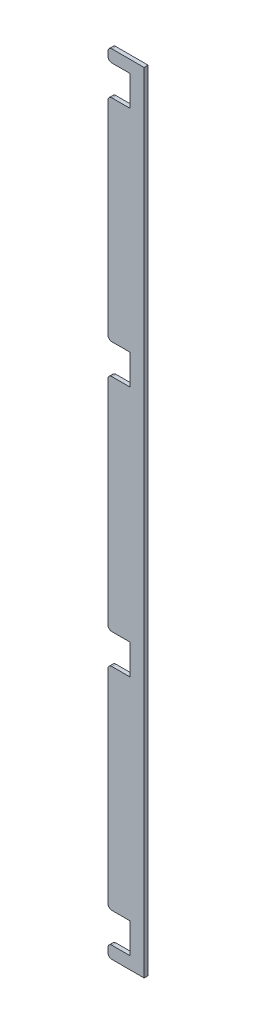
SolidWorks part; units mm, degrees
ref_plane "Front Plane" through (0, 0, 0) normal (0, 0, 1) x (1, 0, 0)
ref_plane "Top Plane" through (0, 0, 0) normal (0, 1, 0) x (1, 0, 0)
ref_plane "Right Plane" through (0, 0, 0) normal (1, 0, 0) x (0, 0, -1)
sketch "Sketch1" plane through (0, 0, 0) normal (0, 0, 1) x (1, 0, 0)
  line L0 (0, -182.5952) -> (-4.5, -182.5952)
  line L2 (0, 13.4048) -> (0, -182.5952)
  line L6 (-4.5, 10.3548) -> (-3.5, 10.3548)
  line L7 (-3.5, 10.3548) -> (-3.5, 2.8548)
  line L8 (0, 2.4048) -> (0, -6.5952) construction
  line L9 (-3.5, 2.8548) -> (-4.5, 2.8548)
  line L10 (-4.5, -49.6452) -> (-3.5, -49.6452)
  line L11 (-3.5, -49.6452) -> (-3.5, -57.1452)
  line L12 (-3.5, -57.1452) -> (-4.5, -57.1452)
  line L13 (-4.5, -112.0452) -> (-3.5, -112.0452)
  line L14 (-3.5, -112.0452) -> (-3.5, -119.5452)
  line L15 (-3.5, -119.5452) -> (-4.5, -119.5452)
  line L16 (-4.5, -172.0452) -> (-3.5, -172.0452)
  line L17 (-3.5, -172.0452) -> (-3.5, -179.5452)
  line L18 (-3.5, -179.5452) -> (-4.5, -179.5452)
  line L100 (-8, 10.3548) -> (-4.5, 10.3548)
  line L101 (-4.5, 10.3548) -> (-4.5, 2.8548)
  line L102 (-4.5, 2.8548) -> (-8, 2.8548)
  line L103 (-9, 1.8548) -> (-9, -48.6452)
  line L104 (-8, -49.6452) -> (-4.5, -49.6452)
  line L105 (-4.5, -49.6452) -> (-4.5, -57.1452)
  line L106 (-4.5, -57.1452) -> (-8, -57.1452)
  line L107 (-9, -58.1452) -> (-9, -111.0452)
  line L108 (-8, -112.0452) -> (-4.5, -112.0452)
  line L109 (-4.5, -112.0452) -> (-4.5, -119.5452)
  line L110 (-4.5, -119.5452) -> (-8, -119.5452)
  line L111 (-9, -120.5452) -> (-9, -171.0452)
  line L112 (-8, -172.0452) -> (-4.5, -172.0452)
  line L113 (-4.5, -172.0452) -> (-4.5, -179.5452)
  line L114 (-4.5, -179.5452) -> (-8, -179.5452)
  line L115 (-9, -180.5452) -> (-9, -181.5952)
  line L116 (-8, -182.5952) -> (-4.5, -182.5952)
  line L117 (-4.5, -182.5952) -> (-4.5, -191.5952)
  line L118 (-4.5, -191.5952) -> (78.5, -191.5952)
  line L119 (78.5, -191.5952) -> (78.5, -182.5952)
  line L120 (78.5, -182.5952) -> (82, -182.5952)
  line L121 (83, -181.5952) -> (83, -180.5452)
  line L122 (82, -179.5452) -> (78.5, -179.5452)
  line L123 (78.5, -179.5452) -> (78.5, -172.0452)
  line L124 (78.5, -172.0452) -> (82, -172.0452)
  line L125 (83, -171.0452) -> (83, -120.5452)
  line L126 (82, -119.5452) -> (78.5, -119.5452)
  line L127 (78.5, -119.5452) -> (78.5, -112.0452)
  line L128 (78.5, -112.0452) -> (82, -112.0452)
  line L129 (83, -111.0452) -> (83, -58.1452)
  line L130 (82, -57.1452) -> (78.5, -57.1452)
  line L131 (78.5, -57.1452) -> (78.5, -49.6452)
  line L132 (78.5, -49.6452) -> (82, -49.6452)
  line L133 (83, -48.6452) -> (83, 1.8548)
  line L134 (82, 2.8548) -> (78.5, 2.8548)
  line L135 (78.5, 2.8548) -> (78.5, 10.3548)
  line L136 (78.5, 10.3548) -> (82, 10.3548)
  line L137 (83, 11.3548) -> (83, 12.4048)
  line L138 (82, 13.4048) -> (78.5, 13.4048)
  line L139 (78.5, 13.4048) -> (78.5, 22.4048)
  line L140 (78.5, 22.4048) -> (-4.5, 22.4048)
  line L141 (-4.5, 22.4048) -> (-4.5, 13.4048)
  line L142 (-4.5, 13.4048) -> (-8, 13.4048)
  line L143 (-9, 12.4048) -> (-9, 11.3548)
  line L144 (-8, 10.3548) -> (-4.5, 10.3548)
  line L145 (-4.5, 10.3548) -> (-4.5, 2.8548)
  line L146 (-4.5, 2.8548) -> (-8, 2.8548)
  line L147 (-9, 1.8548) -> (-9, -48.6452)
  line L148 (-8, -49.6452) -> (-4.5, -49.6452)
  line L149 (-4.5, -49.6452) -> (-4.5, -57.1452)
  line L150 (-4.5, -57.1452) -> (-8, -57.1452)
  line L151 (-9, -58.1452) -> (-9, -111.0452)
  line L152 (-8, -112.0452) -> (-4.5, -112.0452)
  line L153 (-4.5, -112.0452) -> (-4.5, -119.5452)
  line L154 (-4.5, -119.5452) -> (-8, -119.5452)
  line L155 (-9, -120.5452) -> (-9, -171.0452)
  line L156 (-8, -172.0452) -> (-4.5, -172.0452)
  line L157 (-4.5, -172.0452) -> (-4.5, -179.5452)
  line L158 (-4.5, -179.5452) -> (-8, -179.5452)
  line L159 (-9, -180.5452) -> (-9, -181.5952)
  line L160 (-8, -182.5952) -> (-4.5, -182.5952)
  line L186 (0, 13.4048) -> (-8, 13.4048)
  line L187 (-9, 12.4048) -> (-9, 11.3548)
  arc A40 (-8, 2.8548) -> (-9, 1.8548) centre (-8, 1.8548) ccw
  arc A41 (-9, -48.6452) -> (-8, -49.6452) centre (-8, -48.6452) ccw
  arc A42 (-8, -57.1452) -> (-9, -58.1452) centre (-8, -58.1452) ccw
  arc A43 (-9, -111.0452) -> (-8, -112.0452) centre (-8, -111.0452) ccw
  arc A44 (-8, -119.5452) -> (-9, -120.5452) centre (-8, -120.5452) ccw
  arc A45 (-9, -171.0452) -> (-8, -172.0452) centre (-8, -171.0452) ccw
  arc A46 (-8, -179.5452) -> (-9, -180.5452) centre (-8, -180.5452) ccw
  arc A47 (-9, -181.5952) -> (-8, -182.5952) centre (-8, -181.5952) ccw
  arc A48 (82, -182.5952) -> (83, -181.5952) centre (82, -181.5952) ccw
  arc A49 (83, -180.5452) -> (82, -179.5452) centre (82, -180.5452) ccw
  arc A50 (82, -172.0452) -> (83, -171.0452) centre (82, -171.0452) ccw
  arc A51 (83, -120.5452) -> (82, -119.5452) centre (82, -120.5452) ccw
  arc A52 (82, -112.0452) -> (83, -111.0452) centre (82, -111.0452) ccw
  arc A53 (83, -58.1452) -> (82, -57.1452) centre (82, -58.1452) ccw
  arc A54 (82, -49.6452) -> (83, -48.6452) centre (82, -48.6452) ccw
  arc A55 (83, 1.8548) -> (82, 2.8548) centre (82, 1.8548) ccw
  arc A56 (82, 10.3548) -> (83, 11.3548) centre (82, 11.3548) ccw
  arc A57 (83, 12.4048) -> (82, 13.4048) centre (82, 12.4048) ccw
  arc A58 (-8, 13.4048) -> (-9, 12.4048) centre (-8, 12.4048) ccw
  arc A59 (-9, 11.3548) -> (-8, 10.3548) centre (-8, 11.3548) ccw
  arc A60 (-8, 2.8548) -> (-9, 1.8548) centre (-8, 1.8548) ccw
  arc A61 (-9, -48.6452) -> (-8, -49.6452) centre (-8, -48.6452) ccw
  arc A62 (-8, -57.1452) -> (-9, -58.1452) centre (-8, -58.1452) ccw
  arc A63 (-9, -111.0452) -> (-8, -112.0452) centre (-8, -111.0452) ccw
  arc A64 (-8, -119.5452) -> (-9, -120.5452) centre (-8, -120.5452) ccw
  arc A65 (-9, -171.0452) -> (-8, -172.0452) centre (-8, -171.0452) ccw
  arc A66 (-8, -179.5452) -> (-9, -180.5452) centre (-8, -180.5452) ccw
  arc A67 (-9, -181.5952) -> (-8, -182.5952) centre (-8, -181.5952) ccw
  arc A78 (-8, 13.4048) -> (-9, 12.4048) centre (-8, 12.4048) ccw
  arc A79 (-9, 11.3548) -> (-8, 10.3548) centre (-8, 11.3548) ccw
  point P9 (-3.5, -172.0452)
  point P10 (-3.5, -119.5452)
  dimension "D1" = 1
  dimension "D2" = 0
extrude "Boss-Extrude1" add sketch "Sketch1" along normal blind 1 contours L2 region at (-4.3134, -84.5952, 0)
